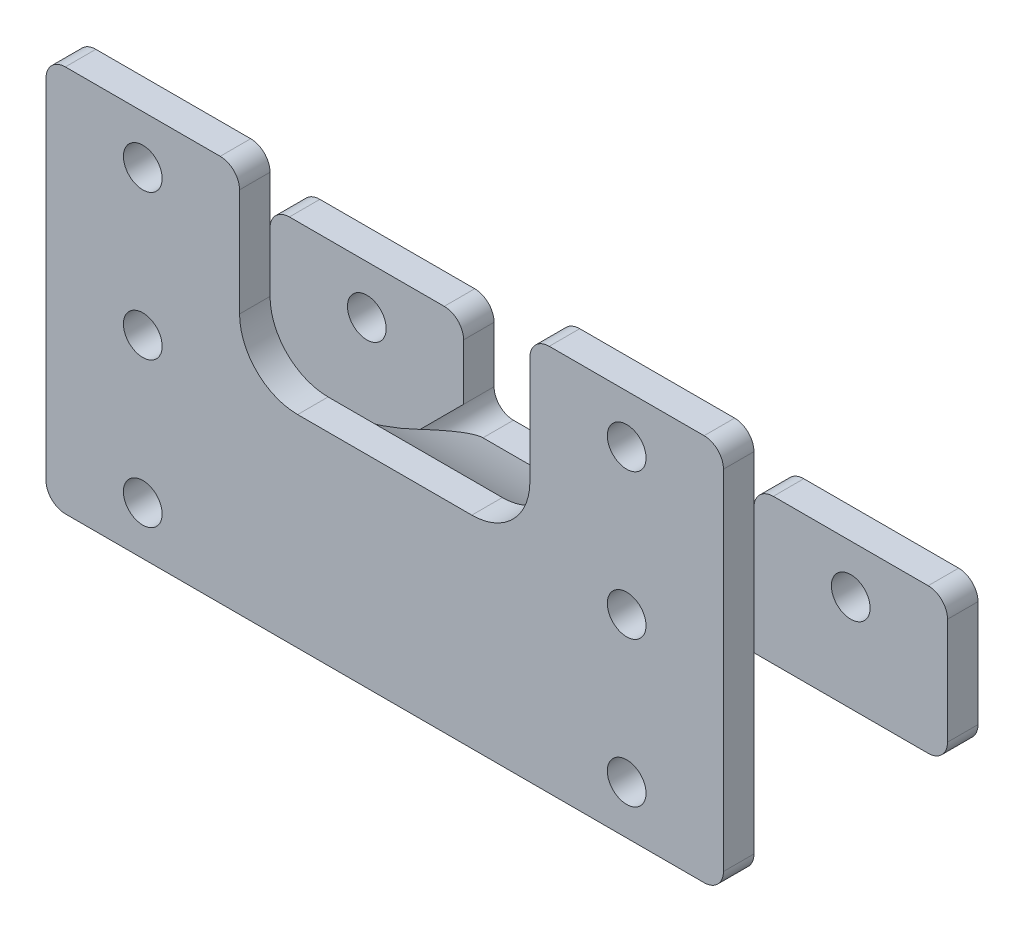
SolidWorks part; units mm, degrees
material "ABS"
ref_plane "Front Plane" through (0, 0, 0) normal (0, 0, 1) x (1, 0, 0)
ref_plane "Top Plane" through (0, 0, 0) normal (0, 1, 0) x (1, 0, 0)
ref_plane "Right Plane" through (0, 0, 0) normal (1, 0, 0) x (0, 0, -1)
sketch "Sketch1" plane through (0, 0, 0) normal (0, 0, 1) x (1, 0, 0)
  line L0 (-12.7, 0) -> (12.7, 0) construction
  line L2 (-12.7, 431.8) -> (-12.7, 0) construction
  line L4 (50.8, 431.8) -> (50.8, 0) construction
  line L5 (50.8, 0) -> (76.2, 0) construction
  line L6 (-12.7, 0) -> (12.7, 0)
  line L7 (12.7, 431.8) -> (12.7, 0) construction
  line L8 (-12.7, 50.8) -> (-12.7, 0)
  line L9 (12.7, 50.8) -> (12.7, 0)
  line L10 (50.8, 50.8) -> (50.8, 0)
  line L11 (50.8, 0) -> (76.2, 0)
  line L12 (12.7, 0) -> (50.8, 0) construction
  line L13 (31.75, 0) -> (31.75, 4.8047)
  line L14 (-12.7, 50.8) -> (12.7, 50.8)
  line L15 (76.2, 0) -> (76.2, 431.8) construction
  line L16 (50.8, 50.8) -> (76.2, 50.8)
  line L17 (76.2, 50.8) -> (76.2, 0)
  circle A0 centre (0, 6.35) radius 2.54
  circle A1 centre (0, 25.4) radius 2.54
  circle A2 centre (0, 44.45) radius 2.54
  circle A3 centre (63.5, 44.45) radius 2.54
  circle A4 centre (63.5, 25.4) radius 2.54
  circle A5 centre (63.5, 6.35) radius 2.54
  dimension "D1" = 5.08
  dimension "D2" = 6.35
  dimension "D4" = 50.8
  dimension "D3" = 3
extrude "Boss-Extrude1" add sketch "Sketch1" along normal blind 4 contours L14 L8 L6 L9 A2 A1 A0 | L17 L16 L10 L11 A4 A3 A5
sketch "Sketch2" plane through (50.8, 0, 0) normal (-1, 0, 0) x (0, 0, 1)
  line L1 (0, 26.5314) -> (4, 26.5314)
  line L3 (0, 0) -> (4, 0)
  line L4 (0, 431.8) -> (-25.4, 431.8)
  line L5 (-25.4, 431.8) -> (-25.4, 0)
  line L6 (-25.4, 0) -> (0, 0)
  line L7 (0, 0) -> (0, 431.8)
  line L8 (0, 431.8) -> (-25.4, 431.8)
  line L9 (-25.4, 6.6485) -> (-25.4, 0)
  line L10 (-25.4, 0) -> (0, 0)
  line L12 (4, 26.5314) -> (4, 0)
  circle A0 centre (-44.45, 57.15) radius 2.159 construction
  circle A1 centre (-44.45, 57.15) radius 2.159 construction
  arc A2 (-25.4, 6.6485) -> (0, 26.5314) centre (-44.45, 57.15) ccw
  line M6 (-25.4, 431.8) -> (-25.4, 0)
  line M7 (-25.4, 0) -> (0, 0)
  line M8 (0, 0) -> (0, 431.8)
  dimension "D2" = 107.95
  dimension "D1" = 0
extrude "Boss-Extrude2" add sketch "Sketch2" along normal up to surface (38.1 mm away) contours A2 M6 M7 M8 | L12 L1 L3 M8 up to face at (12.7, 25.4, 2)
sketch "Sketch3" plane through (0, 0, -25.4) normal (0, 0, -1) x (-1, 0, 0)
  line L0 (-31.75, 0) -> (-31.75, 6.6485)
  line L1 (-12.7, 0) -> (-50.8, 0) construction
  line L2 (-12.7, 6.6485) -> (-50.8, 6.6485) construction
  line L3 (-12.7, 0) -> (12.7, 0) construction
  line L4 (12.7, 19.05) -> (-12.7, 19.05)
  line L5 (12.7, 431.8) -> (12.7, 0) construction
  line L6 (-76.2, 0) -> (-76.2, 431.8) construction
  line L7 (12.7, 19.05) -> (12.7, 0)
  line L8 (-76.2, 19.05) -> (-76.2, 0)
  line L9 (12.7, 0) -> (-76.2, 0)
  line L10 (-12.7, 6.6485) -> (-12.7, 19.05)
  line L11 (-12.7, 431.8) -> (-12.7, 0) construction
  line L12 (-50.8, 6.6485) -> (-50.8, 19.05)
  line L13 (-50.8, 0) -> (-50.8, 431.8) construction
  line L14 (-12.7, 6.6485) -> (-50.8, 6.6485)
  line L15 (-50.8, 19.05) -> (-76.2, 19.05)
  circle A0 centre (0, 12.7) radius 2.54
  circle A1 centre (-63.5, 12.7) radius 2.54
  line M3 (-12.7, 0) -> (12.7, 0)
  line M4 (12.7, 0) -> (12.7, 431.8)
  line M6 (-12.7, 431.8) -> (-12.7, 0)
  dimension "D1" = 5.08
  dimension "D2" = 12.7
  dimension "D3" = 19.05
extrude "Boss-Extrude3" add sketch "Sketch3" along normal blind 4 contours L4 A0 M4 M6 M3 | L14 L0 L9 M6 | L12 L15 L8 L9 L0 L14 A1
fillet "Fillet1" radius 7.62 2 edges at (12.7, 26.5314, 2) (50.8, 26.5314, 2)
fillet "Fillet2" radius 2.54 14 edges at (-12.7, 0, -27.4) (76.2, 0, -27.4) (50.8, 19.05, -27.4) (50.8, 6.6485, -27.4) (12.7, 6.6485, -27.4) (12.7, 19.05, -27.4) (-12.7, 19.05, -27.4) (76.2, 19.05, -27.4) (12.7, 50.8, 2) (50.8, 50.8, 2) (76.2, 0, 2) (-12.7, 0, 2) (-12.7, 50.8, 2) (76.2, 50.8, 2)
